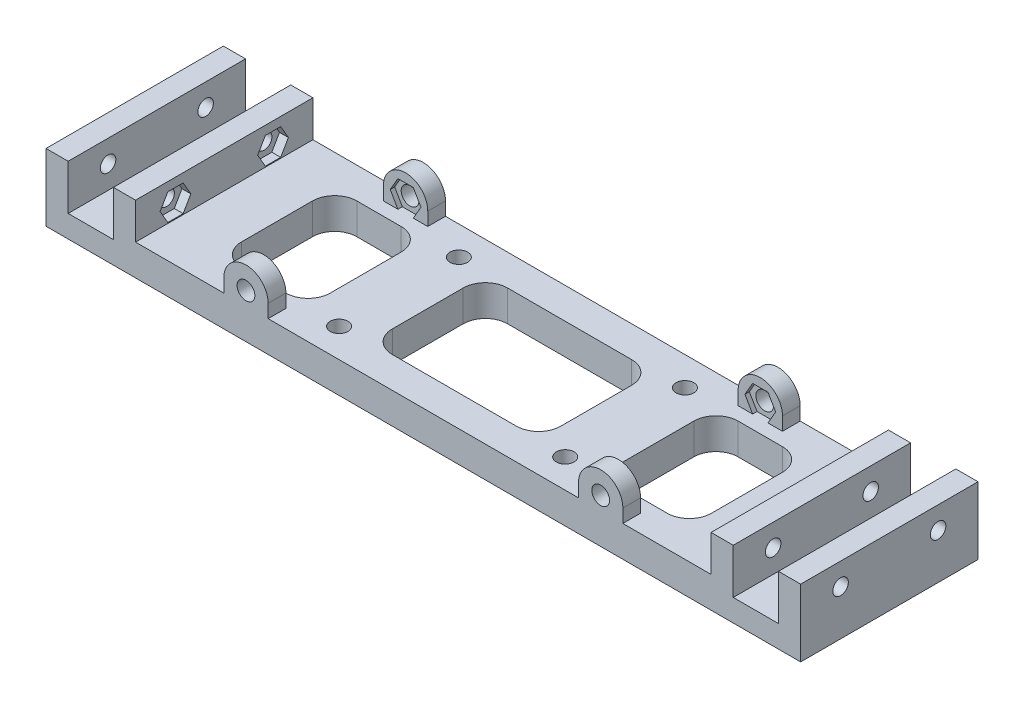
SolidWorks part; units mm, degrees
material "ABS"
ref_plane "Płaszczyzna przednia" through (0, 0, 0) normal (0, 0, 1) x (1, 0, 0)
ref_plane "Płaszczyzna górna" through (0, 0, 0) normal (0, 1, 0) x (1, 0, 0)
ref_plane "Płaszczyzna prawa" through (0, 0, 0) normal (1, 0, 0) x (0, 0, -1)
sketch "Szkic1" plane through (0, 0, 0) normal (0, 0, 1) x (1, 0, 0)
  line L0 (0, 0) -> (0, 47.3092) construction
  line L1 (-80.1, 5.1) -> (-69.9, 5.1)
  line L2 (-80.1, 5.1) -> (-80.1, -5.1)
  line L3 (-80.1, -5.1) -> (-69.9, -5.1)
  line L4 (-69.9, 5.1) -> (-69.9, -5.1)
  line L5 (-80.1, 5.1) -> (-69.9, -5.1) construction
  line L6 (-80.1, -5.1) -> (-69.9, 5.1) construction
  line L7 (69.8998, 5.1002) -> (80.1002, 5.1002)
  line L8 (69.8998, 5.1002) -> (69.8998, -5.1002)
  line L9 (69.8998, -5.1002) -> (80.1002, -5.1002)
  line L10 (80.1002, 5.1002) -> (80.1002, -5.1002)
  line L11 (69.8998, 5.1002) -> (80.1002, -5.1002) construction
  line L12 (69.8998, -5.1002) -> (80.1002, 5.1002) construction
  line L13 (-80.1, 5.1) -> (-85.1, 5.1)
  line L14 (-85.1, 5.1) -> (-85.1, -10.1)
  line L15 (-85.1, -10.1) -> (85.1, -10.1)
  line L16 (85.1, -10.1) -> (85.1, 5.1002)
  line L17 (85.1, 5.1002) -> (80.1002, 5.1002)
  line L18 (69.8998, 5.1002) -> (64.8998, 5.1002)
  line L19 (64.8998, 5.1002) -> (64.8998, -3.1)
  line L20 (64.8998, -3.1) -> (-64.9, -3.1)
  line L21 (-64.9, -3.1) -> (-64.9, 5.1)
  line L22 (-64.9, 5.1) -> (-69.9, 5.1)
  point P0 (-75, 0)
  point P5 (75, 0)
  dimension "D1" = 10.2
  dimension "D2" = 10.2004
  dimension "D3" = 150
  dimension "D4" = 4.9998
  dimension "D5" = 5
  dimension "D6" = 5
  dimension "D7" = 5
  dimension "D8" = 5
  dimension "D9" = 7
extrude "Dodanie-wyciągnięcie1" add sketch "Szkic1" along normal blind 40 contours L21 L22 L4 L3 L2 L13 L14 L15 L16 L17 L10 L9 L8 L18 L19 L20 region at (-0.0002, -5.7295, 0)
sketch "Szkic2" plane through (0, -10.1, 0) normal (0, -1, 0) x (1, 0, 0)
  line L0 (85.1, 20) -> (-85.1, 20) construction
  line L1 (85.1, 40) -> (85.1, 0) construction
  line L2 (-85.1, 40) -> (-85.1, 0) construction
  line L3 (0, 0) -> (0, 40) construction
  line L4 (-85.1, 40) -> (85.1, 40) construction
  circle A0 centre (-25.5, 33.5) radius 2
  circle A1 centre (-25.5, 6.5) radius 2
  circle A2 centre (25.5, 6.5) radius 2
  circle A3 centre (25.5, 33.5) radius 2
  point P8 (0, 0)
  dimension "D1" = 4
  dimension "D2" = 27
  dimension "D3" = 51
extrude "Wytnij-wyciągnięcie1" cut sketch "Szkic2" against normal blind 35
sketch "Szkic3" plane through (0, -10.1, 0) normal (0, -1, 0) x (1, 0, 0)
  line L0 (85.1, 20) -> (-85.1, 20) construction
  line L1 (-19, 33) -> (19, 33)
  line L2 (-19, 33) -> (-19, 7)
  line L3 (-19, 7) -> (19, 7)
  line L4 (19, 33) -> (19, 7)
  line L5 (-19, 33) -> (19, 7) construction
  line L6 (-19, 7) -> (19, 33) construction
  line L7 (85.1, 40) -> (85.1, 0) construction
  line L8 (-85.1, 40) -> (-85.1, 0) construction
  line L9 (0, 0) -> (0, 40) construction
  line L10 (-85.1, 40) -> (85.1, 40) construction
  line L12 (-53, 7) -> (-33, 7)
  line L13 (-53, 7) -> (-53, 33)
  line L14 (-53, 33) -> (-33, 33)
  line L15 (-33, 7) -> (-33, 33)
  line L16 (-53, 7) -> (-33, 33) construction
  line L17 (-53, 33) -> (-33, 7) construction
  line L18 (33, 7) -> (53, 7)
  line L19 (33, 7) -> (33, 33)
  line L20 (33, 33) -> (53, 33)
  line L21 (53, 7) -> (53, 33)
  line L22 (33, 7) -> (53, 33) construction
  line L23 (33, 33) -> (53, 7) construction
  point P0 (0, 20)
  point P16 (43, 20)
  point P17 (0, 20)
  point P18 (-43, 20)
  dimension "D1" = 26
  dimension "D2" = 38
  dimension "D3" = 26
  dimension "D4" = 20
  dimension "D5" = 26
  dimension "D6" = 20
  dimension "D7" = 14
  dimension "D8" = 14
extrude "Wytnij-wyciągnięcie2" cut sketch "Szkic3" against normal blind 35
fillet "Zaokrąglenie1" radius 5 12 edges at (53, -6.6, 33) (53, -6.6, 7) (33, -6.6, 33) (33, -6.6, 7) (19, -6.6, 33) (19, -6.6, 7) (-19, -6.6, 7) (-19, -6.6, 33) (-53, -6.6, 33) (-33, -6.6, 33) (-33, -6.6, 7) (-53, -6.6, 7)
sketch "Szkic4" plane through (85.1, 0, 0) normal (1, 0, 0) x (0, 0, -1)
  line L0 (-20, -10.1) -> (-20, 5.1002) construction
  line L1 (-40, -10.1) -> (0, -10.1) construction
  line L2 (-40, 5.1002) -> (0, 5.1002) construction
  circle A0 centre (-31, 0.1002) radius 1.75
  circle A1 centre (-9, 0.1002) radius 1.75
  point P4 (0, 0)
  dimension "D1" = 3.5
  dimension "D2" = 22
  dimension "D3" = 5
extrude "Wytnij-wyciągnięcie3" cut sketch "Szkic4" against normal blind 35
sketch "Szkic5" plane through (85.1, 0, 0) normal (1, 0, 0) x (0, 0, -1)
  line L1 (-29.2679, 3.1002) -> (-32.7321, 3.1002)
  line L2 (-32.7321, 3.1002) -> (-34.4641, 0.1002)
  line L3 (-34.4641, 0.1002) -> (-32.7321, -2.8998)
  line L4 (-32.7321, -2.8998) -> (-29.2679, -2.8998)
  line L5 (-29.2679, -2.8998) -> (-27.5359, 0.1002)
  line L6 (-27.5359, 0.1002) -> (-29.2679, 3.1002)
  line L7 (-7.2679, 3.1002) -> (-10.7321, 3.1002)
  line L8 (-10.7321, 3.1002) -> (-12.4641, 0.1002)
  line L9 (-12.4641, 0.1002) -> (-10.7321, -2.8998)
  line L10 (-10.7321, -2.8998) -> (-7.2679, -2.8998)
  line L11 (-7.2679, -2.8998) -> (-5.5359, 0.1002)
  line L12 (-5.5359, 0.1002) -> (-7.2679, 3.1002)
  circle A0 centre (-31, 0.1002) radius 3 construction
  circle A1 centre (-9, 0.1002) radius 3 construction
  point P10 (-29.1986, 3.0591)
  point P19 (-7.4262, 3.0061)
  point P20 (-29.2008, 3.0604)
  dimension "D1" = 6
extrude "Wytnij-wyciągnięcie4" cut sketch "Szkic5" along normal blind 2 from surface starting at face at (64.8998, 0.1002, 29.25)
mirror "Lustro1" about plane through (0, 0, 0) normal (1, 0, 0) of "Wytnij-wyciągnięcie3"
extrude "Wytnij-wyciągnięcie5" cut sketch "Szkic5<2>" against normal blind 2 from surface starting at face at (-64.9, 0.1002, 32.75)
sketch "Szkic5<2>" plane through (85.1, 0, 0) normal (1, 0, 0) x (0, 0, -1) same geometry as "Szkic5"
sketch "Szkic7" plane through (0, 0, 40) normal (0, 0, 1) x (1, 0, 0)
  line L0 (0, -10.1) -> (0, 0) construction
  line L1 (-85.1, -10.1) -> (85.1, -10.1) construction
  line L2 (64.8998, -3.1) -> (-64.9, -3.1) construction
  line L3 (-45, -0.1) -> (-45, -3.1)
  line L4 (-35, -0.1) -> (-35, -3.1)
  line L5 (35, -0.1) -> (35, -3.1)
  line L6 (45, -0.1) -> (45, -3.1)
  line L7 (64.8998, -3.1) -> (-64.9, -3.1)
  circle A0 centre (40, -0.1) radius 2
  circle A1 centre (-40, -0.1) radius 2
  arc A2 (-35, -0.1) -> (-45, -0.1) centre (-40, -0.1) ccw
  arc A3 (45, -0.1) -> (35, -0.1) centre (40, -0.1) ccw
  line M17 (64.8998, -3.1) -> (-64.9, -3.1)
  dimension "D1" = 80
  dimension "D3" = 4
  dimension "D4" = 10
  dimension "D2" = 3
extrude "Dodanie-wyciągnięcie4" add sketch "Szkic7" against normal blind 4 contours L6 A3 L5 A0 M17 | L4 A2 L3 A1 M17 region at (-40, 4.7719, 40) region at (35.1281, -1.6, 40)
sketch "Szkic8" plane through (0, 0, 36) normal (0, 0, -1) x (-1, 0, 0)
  line L1 (-36.5359, -0.1) -> (-38.2679, 2.9)
  line L2 (-38.2679, 2.9) -> (-41.7321, 2.9)
  line L3 (-41.7321, 2.9) -> (-43.4641, -0.1)
  line L4 (-43.4641, -0.1) -> (-41.7321, -3.1)
  line L5 (-41.7321, -3.1) -> (-38.2679, -3.1)
  line L6 (-38.2679, -3.1) -> (-36.5359, -0.1)
  line L7 (43.4641, -0.1) -> (41.7321, 2.9)
  line L8 (41.7321, 2.9) -> (38.2679, 2.9)
  line L9 (38.2679, 2.9) -> (36.5359, -0.1)
  line L10 (36.5359, -0.1) -> (38.2679, -3.1)
  line L11 (38.2679, -3.1) -> (41.7321, -3.1)
  line L12 (41.7321, -3.1) -> (43.4641, -0.1)
  circle A0 centre (-40, -0.1) radius 3 construction
  circle A1 centre (40, -0.1) radius 3 construction
  point P10 (0, 0)
  point P19 (0, 0)
  dimension "D1" = 6
extrude "Wytnij-wyciągnięcie6" cut sketch "Szkic8" against normal blind 1
ref_plane "Płaszczyzna1" through (0, 0, 20) normal (0, 0, -1) x (-1, 0, 0)
mirror "Lustro3" about plane through (0, 0, 20) normal (0, 0, -1) of "Wytnij-wyciągnięcie6", "Dodanie-wyciągnięcie4"
